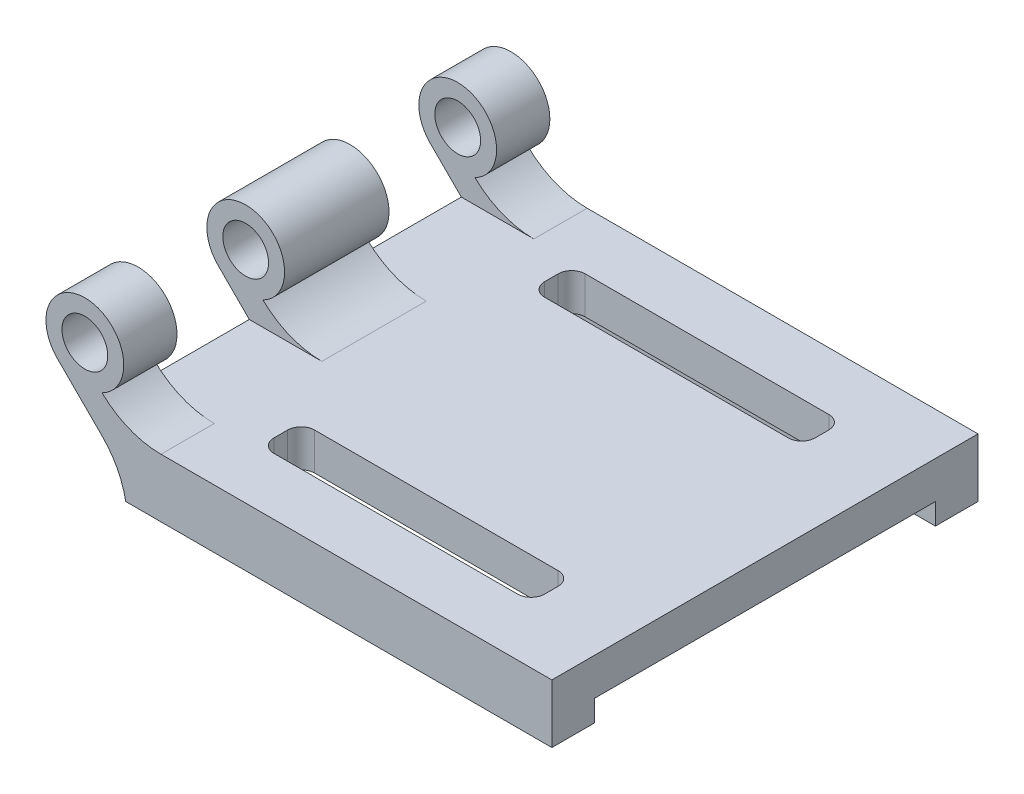
SolidWorks part; units mm, degrees
ref_plane "前视基准面" through (0, 0, 0) normal (0, 0, 1) x (1, 0, 0)
ref_plane "上视基准面" through (0, 0, 0) normal (0, 1, 0) x (1, 0, 0)
ref_plane "右视基准面" through (0, 0, 0) normal (1, 0, 0) x (0, 0, -1)
other "Configuration Table"
sketch "草图1" plane through (0, 0, 0) normal (0, 0, 1) x (1, 0, 0)
  line L0 (-20, 1.75) -> (-22.2255, 3.9755)
  line L1 (-20, -1.75) -> (20, -1.75)
  line L3 (-20, 1.75) -> (20, 1.75)
  line L4 (20, -1.75) -> (20, 1.75)
  line L5 (0, 1.75) -> (0, -1.75) construction
  line L6 (-22.5, 0) -> (20, 0) construction
  line L7 (-20, -1.75) -> (-26.4191, 4.6691)
  arc A0 (-22.2255, 3.9755) -> (-26.4191, 4.6691) centre (-23.8381, 7.25) ccw
  circle A1 centre (-23.8381, 7.25) radius 2.15
  point P0 (0, 0)
  dimension "D5" = 7.3
  dimension "D6" = 1.5
  dimension "D1" = 40
  dimension "D2" = 3.5
  dimension "D3" = 9
  dimension "D4" = 225
extrude "凸台-拉伸1" add sketch "草图1" along normal blind 40
ref_plane "基准面1" through (-20.1881, 0, 0) normal (1, 0, 0) x (0, 0, -1)
sketch "草图2" plane through (-20.1881, 0, 0) normal (1, 0, 0) x (0, 0, -1)
  line L0 (0, 1.75) -> (0, 3.9755) construction
  line L1 (0, 3.9755) -> (0, 10.9) construction
  line L2 (-40, 1.75) -> (-40, 3.9755) construction
  line L3 (-40, 10.9) -> (-40, 3.9755) construction
  line L4 (0, 1.75) -> (0, 3.9755) construction
  line L5 (0, 3.9755) -> (0, 10.9) construction
  line L6 (-40, 1.75) -> (-40, 3.9755) construction
  line L7 (-40, 10.9) -> (-40, 3.9755) construction
  line L9 (-35, 11.75) -> (-24.9, 11.75)
  line L10 (-35, 11.75) -> (-35, 1.75)
  line L11 (-35, 1.75) -> (-24.9, 1.75)
  line L12 (-24.9, 11.75) -> (-24.9, 1.75)
  line L13 (-29.95, 1.75) -> (-29.95, 11.75) construction
  line L14 (-35, 6.75) -> (-24.9, 6.75) construction
  line L15 (-40, 1.75) -> (0, 1.75) construction
  line L16 (-40, 3.9755) -> (0, 3.9755) construction
  line L17 (-20, -12.7188) -> (-20, 20.6699) construction
  line L18 (-5, 1.75) -> (-15.1, 1.75)
  line L19 (-15.1, 11.75) -> (-15.1, 1.75)
  line L20 (-5, 11.75) -> (-15.1, 11.75)
  line L21 (-5, 11.75) -> (-5, 1.75)
  point P2 (-29.95, 6.75)
  point P15 (-20, 3.9755)
  dimension "D1" = 10.1
  dimension "D2" = 5
  dimension "D3" = 10
extrude "切除-拉伸2" cut sketch "草图2" against normal blind 10 and the other way through all
sketch "草图4" plane through (0, -1.75, 0) normal (0, -1, 0) x (1, 0, 0)
  line L0 (-20, 0) -> (20, 0) construction
  line L1 (-20, 40) -> (20, 40) construction
  line L2 (-20, 0) -> (20, 0)
  line L3 (-20, 40) -> (20, 40)
  line L4 (-20, 40) -> (-20, 36)
  line L5 (-20, 40) -> (-20, 0) construction
  line L6 (-20, 36) -> (20, 36)
  line L7 (20, 40) -> (20, 0) construction
  line L8 (20, 36) -> (20, 40)
  line L9 (-20, 0) -> (-20, 4)
  line L10 (-20, 4) -> (20, 4)
  line L11 (20, 4) -> (20, 0)
  dimension "D1" = 4
  dimension "D2" = 4
extrude "凸台-拉伸2" add sketch "草图4" along normal blind 2
sketch "草图5" plane through (0, 1.75, 0) normal (0, 1, 0) x (1, 0, 0)
  line L0 (0, 0) -> (0, -40) construction
  line L1 (20, -40) -> (-20, -40) construction
  line L2 (11.4143, -30.8229) -> (-11.4457, -30.8229)
  line L3 (12.6843, -33.3629) -> (12.6843, -32.0929)
  line L4 (-11.4457, -34.6329) -> (11.4143, -34.6329)
  line L5 (-12.7157, -32.0929) -> (-12.7157, -33.3629)
  line L6 (12.6843, -7.9629) -> (12.6843, -6.6929)
  line L7 (-11.4457, -9.2329) -> (11.4143, -9.2329)
  line L8 (-12.7157, -6.6929) -> (-12.7157, -7.9629)
  line L9 (11.4143, -5.4229) -> (-11.4457, -5.4229)
  arc A0 (12.6843, -32.0929) -> (11.4143, -30.8229) centre (11.4143, -32.0929) ccw
  arc A1 (11.4143, -34.6329) -> (12.6843, -33.3629) centre (11.4143, -33.3629) ccw
  arc A2 (-12.7157, -33.3629) -> (-11.4457, -34.6329) centre (-11.4457, -33.3629) ccw
  arc A3 (-11.4457, -30.8229) -> (-12.7157, -32.0929) centre (-11.4457, -32.0929) ccw
  arc A4 (12.6843, -6.6929) -> (11.4143, -5.4229) centre (11.4143, -6.6929) ccw
  arc A5 (11.4143, -9.2329) -> (12.6843, -7.9629) centre (11.4143, -7.9629) ccw
  arc A6 (-12.7157, -7.9629) -> (-11.4457, -9.2329) centre (-11.4457, -7.9629) ccw
  arc A7 (-11.4457, -5.4229) -> (-12.7157, -6.6929) centre (-11.4457, -6.6929) ccw
  point P5 (0, -20)
extrude "切除-拉伸3" cut sketch "草图5" against normal up to surface (3.5 mm away) up to face at (0, -1.75, 20)
fillet "圆角1" radius 8 5 edges at (-20, -1.75, 2) (-20, -1.75, 38) (-20, 1.75, 2.5) (-20, 1.75, 20) (-20, 1.75, 37.5)
